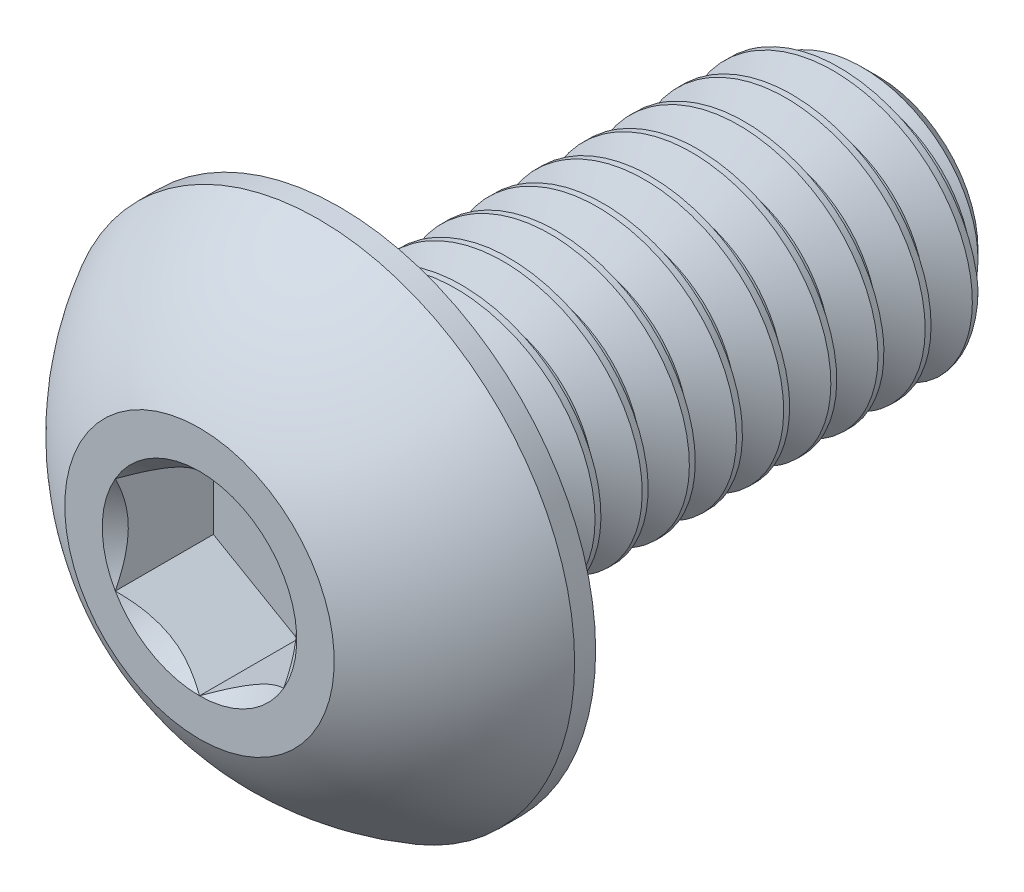
SolidWorks part; units mm, degrees
ref_plane "Front" through (0, 0, 0) normal (0, 0, 1) x (1, 0, 0)
ref_plane "Top" through (0, 0, 0) normal (0, 1, 0) x (1, 0, 0)
ref_plane "Right" through (0, 0, 0) normal (1, 0, 0) x (0, 0, -1)
sketch "Sketch1" plane through (0, 0, 0) normal (1, 0, 0) x (0, 0, -1)
  line L2 (2.08, 2) -> (10.08, 2)
  line L3 (10.08, 2) -> (10.08, 0)
  line L4 (10.08, 0) -> (2.08, 0)
  line L6 (1.768, 3.8) -> (2.08, 3.8) construction
  line L7 (10.08, 2) -> (10.08, -2) construction
  line L8 (0, 0) -> (2.08, 0) construction
  line L9 (2.08, 3.8) -> (2.08, -3.8) construction
  line L11 (2.08, 2) -> (2.08, 0)
  line L13 (0, 1.25) -> (0, -1.25) construction
  line L14 (0, 1.25) -> (0, 2) construction
  arc A3 (0, 2) -> (1.768, 3.8) centre (3.8365, 0) cw construction
  dimension "D1" = 0.312
  dimension "Head Ht" = 2.08
  dimension "Head Dia" = 7.6
  dimension "Dia" = 4
  dimension "Lg" = 8
  dimension "Hex" = 2.5
revolve "Revolve1" add sketch "Sketch1" angle 360 mid plane about L4
sketch "Sketch3" plane through (0, 0, -10.08) normal (0, 0, -1) x (-1, 0, 0)
  circle A0 centre (0, 0) radius 2
curve "Helix/Spiral1" pitch 0.7 height 8.7 radius 2 centre (0, 0, -10.08) axis (0, 0, 1) start towards (0, 1, 0)
sketch "Sketch2" plane through (0, 0, 0) normal (1, 0, 0) x (0, 0, -1)
  line L0 (10.08, 2) -> (10.6925, 2)
  line L1 (10.6925, 2) -> (10.43, 1.5453)
  line L2 (10.43, 1.5453) -> (10.3425, 1.5453)
  line L3 (10.3425, 1.5453) -> (10.08, 2)
  line L4 (10.2112, 1.7727) -> (10.5612, 1.7727) construction
  dimension "D1" = 60
  dimension "D2" = 0.0875
  dimension "D3" = 0.35
chamfer "Chamfer1" distance 0.525 angle 45 1 edges at (0, 2, -10.08)
sweep "Cut-Sweep1" cut profiles "Sketch2" path "Helix/Spiral1" align with end faces yes
sketch "Sketch7" plane through (0, 0, 0) normal (1, 0, 0) x (0, 0, -1)
  line L6 (1.768, 3.8) -> (2.08, 3.8) construction
  line L8 (0, 0) -> (2.08, 0) construction
  line L11 (2.08, 3.8) -> (2.08, -3.8) construction
  line L12 (1.768, 3.8) -> (2.08, 3.8)
  line L13 (0, 0) -> (2.08, 0)
  line L14 (0, 1.25) -> (0, -1.25) construction
  line L15 (2.08, 3.8) -> (2.08, 0)
  line L16 (0, 2) -> (0, 0)
  arc A2 (1.768, 3.8) -> (0, 2) centre (3.8365, 0) ccw construction
  arc A3 (1.768, 3.8) -> (0, 2) centre (3.8365, 0) ccw
revolve "Revolve2" add sketch "Sketch7" angle 360 mid plane about L13
sketch "Sketch5" plane through (0, 0, 0) normal (0, 0, 1) x (1, 0, 0)
  line L1 (1.25, -0.7217) -> (1.25, 0.7217)
  line L2 (1.25, 0.7217) -> (0, 1.4434)
  line L3 (0, 1.4434) -> (-1.25, 0.7217)
  line L4 (-1.25, 0.7217) -> (-1.25, -0.7217)
  line L5 (-1.25, -0.7217) -> (0, -1.4434)
  line L6 (0, -1.4434) -> (1.25, -0.7217)
  circle A0 centre (0, 0) radius 1.25 construction
extrude "Cut-Extrude2" cut sketch "Sketch5" against normal blind 1.456
sketch "Sketch6" plane through (0, 0, 0) normal (0, 0, 1) x (1, 0, 0)
  circle A0 centre (0, 0) radius 1.4434
extrude "Cut-Extrude3" cut sketch "Sketch6" against normal blind 1.456 draft 45
sketch "Sketch9" [suppressed] plane through (0, 0, -6.6) normal (0, 0, 1) x (1, 0, 0)
  circle A2 centre (0, 0) radius 6
extrude "Boss-Extrude2" [suppressed] add sketch "Sketch9" against normal offset from surface (19 mm away) 32 up to face at (0, 1.475, -10.08)
sketch "Sketch10" plane through (0, 0, 0) normal (1, 0, 0) x (0, 0, -1)
  line L0 (10.08, 2) -> (10.08, -2) construction
  point P0 (9.03, -2)
  dimension "D1" = 1.05
equation "\"D3@Helix/Spiral1\" = \"Lg@Sketch1\" + \"D4@Helix/Spiral1\""
equation "\"D2@Sketch2\" = \"D4@Helix/Spiral1\" * .125"
equation "\"D3@Sketch2\" = \"D4@Helix/Spiral1\" * .5"
equation "\"D1@Chamfer1\" = \"D4@Helix/Spiral1\" * .75"
equation "\"D1@Cut-Extrude2\" = \"Head Ht@Sketch1\" * .7"
equation "\"D1@Sketch1\" = \"Head Ht@Sketch1\" * .15"
equation "\"D1@Sketch10\" = \"D4@Helix/Spiral1\" * 1.5"
equation "\"D1@Cut-Extrude3\" = \"D1@Cut-Extrude2\""
